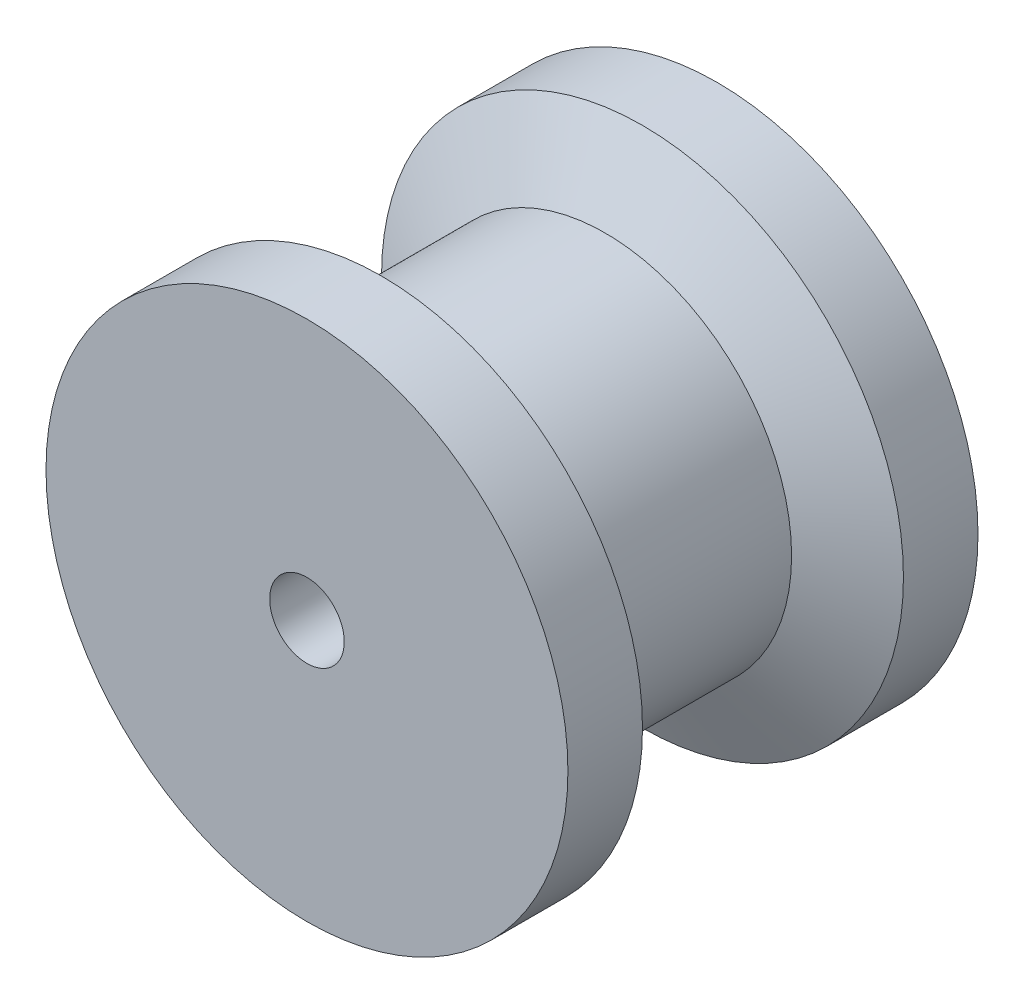
SolidWorks part; units mm, degrees
ref_plane "Front Plane" through (0, 0, 0) normal (0, 0, 1) x (1, 0, 0)
ref_plane "Top Plane" through (0, 0, 0) normal (0, 1, 0) x (1, 0, 0)
ref_plane "Right Plane" through (0, 0, 0) normal (1, 0, 0) x (0, 0, -1)
sketch "Sketch1" plane through (0, 0, 0) normal (0, 0, 1) x (1, 0, 0)
  circle A0 centre (0, 0) radius 7
  circle A1 centre (0, 0) radius 1
  dimension "D1" = 14
  dimension "D2" = 2
extrude "Boss-Extrude1" add sketch "Sketch1" along normal blind 11
sketch "Sketch4" plane through (0, 0, 0) normal (1, 0, 0) x (0, 0, -1)
  line L0 (0, 55) -> (0, -55) construction
  line L1 (-1000, 0) -> (49000, 0) construction
  line L2 (0, 7) -> (-11, 7) construction
  line L3 (-2, 7) -> (-3, 5)
  line L4 (-3, 5) -> (-8, 5)
  line L5 (-8, 5) -> (-9, 7)
  line L6 (-9, 7) -> (-2, 7)
  line L8 (-5.5, -1000) -> (-5.5, 49000) construction
  line L9 (-11, 7) -> (-11, -7) construction
  point P16 (0, 0)
  dimension "D1" = 5
  dimension "D2" = 5.5
  dimension "D3" = 2
  dimension "D4" = 2
  dimension "D5" = 2
revolve "Cut-Revolve1" cut sketch "Sketch4" angle 360 about L1
ref_axis "Axis1" through (0, 0, 25.8802) along (0, 0, -1)
